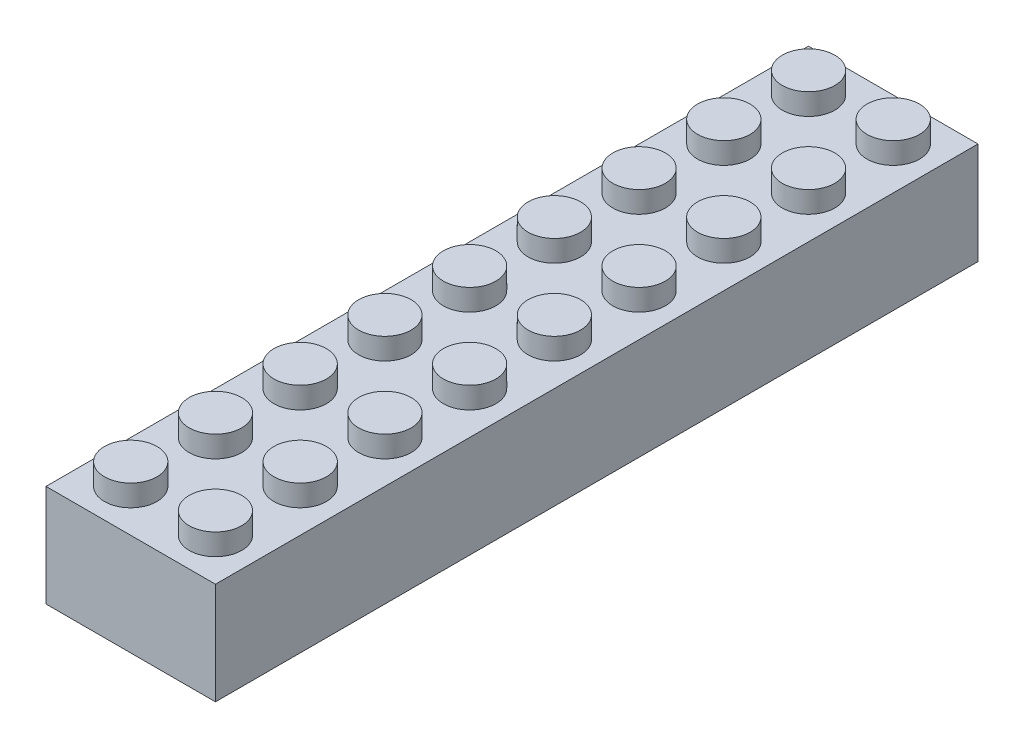
SolidWorks part; units mm, degrees
ref_plane "Front Plane" through (0, 0, 0) normal (0, 0, 1) x (1, 0, 0)
ref_plane "Top Plane" through (0, 0, 0) normal (0, 1, 0) x (1, 0, 0)
ref_plane "Right Plane" through (0, 0, 0) normal (1, 0, 0) x (0, 0, -1)
sketch "stencil" plane through (0, 0, 0) normal (0, 1, 0) x (1, 0, 0)
  line L2 (7.9, 71.1) -> (7.9, 0) construction
  line L29 (14.3, 1.5) -> (1.5, 1.5)
  line L30 (15.8, 71.1) -> (0, 71.1)
  line L32 (15.8, 71.1) -> (15.8, 0)
  line L34 (15.8, 0) -> (0, 0)
  line L36 (0, 71.1) -> (0, 0)
  line L37 (7.9, 0) -> (7.9, 71.1) construction
  line L38 (15.8, 35.55) -> (0, 35.55) construction
  line L39 (1.5, 69.6) -> (1.5, 1.5)
  line L40 (14.3, 69.6) -> (1.5, 69.6)
  line L41 (14.3, 69.6) -> (14.3, 1.5)
  circle A40 centre (3.95, 3.95) radius 2.45
  circle A41 centre (7.9, 7.9) radius 3.25
  circle A42 centre (3.95, 11.85) radius 2.45
  circle A43 centre (3.95, 19.75) radius 2.45
  circle A44 centre (3.95, 27.65) radius 2.45
  circle A45 centre (7.9, 15.8) radius 3.25
  circle A46 centre (7.9, 23.7) radius 3.25
  circle A47 centre (7.9, 31.6) radius 3.25
  circle A48 centre (3.95, 35.55) radius 2.45
  circle A49 centre (3.95, 43.45) radius 2.45
  circle A50 centre (3.95, 51.35) radius 2.45
  circle A51 centre (7.9, 39.5) radius 3.25
  circle A52 centre (7.9, 47.4) radius 3.25
  circle A53 centre (3.95, 59.25) radius 2.45
  circle A54 centre (3.95, 67.15) radius 2.45
  circle A55 centre (7.9, 55.3) radius 3.25
  circle A56 centre (7.9, 63.2) radius 3.25
  circle A57 centre (7.9, 7.9) radius 2.45
  circle A58 centre (7.9, 15.8) radius 2.45
  circle A59 centre (7.9, 23.7) radius 2.45
  circle A60 centre (7.9, 31.6) radius 2.45
  circle A61 centre (7.9, 39.5) radius 2.45
  circle A62 centre (7.9, 47.4) radius 2.45
  circle A63 centre (7.9, 55.3) radius 2.45
  circle A64 centre (7.9, 63.2) radius 2.45
  circle A65 centre (11.85, 11.85) radius 2.45
  circle A66 centre (11.85, 19.75) radius 2.45
  circle A67 centre (11.85, 27.65) radius 2.45
  circle A68 centre (11.85, 35.55) radius 2.45
  circle A69 centre (11.85, 43.45) radius 2.45
  circle A70 centre (11.85, 51.35) radius 2.45
  circle A71 centre (11.85, 59.25) radius 2.45
  circle A72 centre (11.85, 67.15) radius 2.45
  circle A73 centre (11.85, 3.95) radius 2.45
  point P1 (0, 0)
  point P6 (3.95, -15.8)
  point P9 (7.9, -15.8)
  point P10 (7.9, -11.85)
  point P13 (3.95, -7.9)
  point P15 (7.9, -7.9)
  point P17 (7.9, -3.95)
  point P18 (3.95, 0)
  point P21 (7.9, 0)
  point P25 (7.9, 3.95)
  point P27 (3.95, 7.9)
  point P28 (7.9, 7.9)
  point P29 (0, -11.85)
  point P30 (0, -7.9)
  point P31 (0, 3.95)
  point P34 (0, -3.95)
  point P35 (3.95, 0)
  point P36 (0, 15.8)
  point P37 (0, 23.7)
  point P38 (7.9, 23.7)
  point P39 (15.8, 23.7)
  point P40 (15.8, 15.8)
  point P41 (15.8, 7.9)
  point P43 (7.9, 0)
  point P48 (11.85, 0)
  point P49 (15.8, 0)
  point P50 (3.95, 3.95)
  point P51 (7.9, 3.95)
  point P52 (11.85, 3.95)
  point P53 (15.8, 3.95)
  point P54 (3.95, 7.9)
  point P55 (7.9, 7.9)
  point P56 (11.85, 7.9)
  point P57 (15.8, 7.9)
  point P58 (3.95, 11.85)
  point P59 (7.9, 11.85)
  point P60 (11.85, 11.85)
  point P61 (15.8, 11.85)
  point P63 (3.95, 15.8)
  point P64 (7.9, 15.8)
  point P65 (11.85, 15.8)
  point P66 (15.8, 15.8)
  point P67 (3.95, 19.75)
  point P68 (7.9, 19.75)
  point P69 (11.85, 19.75)
  point P70 (15.8, 19.75)
  point P71 (3.95, 23.7)
  point P72 (7.9, 23.7)
  point P73 (11.85, 23.7)
  point P75 (15.8, 23.7)
  point P77 (3.95, 27.65)
  point P79 (7.9, 27.65)
  point P81 (11.85, 27.65)
  point P83 (15.8, 27.65)
  point P85 (3.95, 31.6)
  point P87 (7.9, 31.6)
  point P88 (11.85, 31.6)
  point P89 (15.8, 31.6)
  point P90 (0, 3.95)
  point P91 (0, 7.9)
  point P92 (0, 11.85)
  point P93 (0, 15.8)
  point P94 (0, 19.75)
  point P95 (0, 23.7)
  point P96 (0, 27.65)
  point P97 (0, 31.6)
  point P113 (0, 35.55)
  point P114 (3.95, 35.55)
  point P115 (7.9, 35.55)
  point P116 (11.85, 35.55)
  point P117 (15.8, 35.55)
  point P118 (0, 39.5)
  point P119 (3.95, 39.5)
  point P120 (7.9, 39.5)
  point P121 (11.85, 39.5)
  point P122 (15.8, 39.5)
  point P124 (0, 43.45)
  point P125 (3.95, 43.45)
  point P126 (7.9, 43.45)
  point P127 (11.85, 43.45)
  point P128 (15.8, 43.45)
  point P129 (0, 47.4)
  point P130 (3.95, 47.4)
  point P131 (7.9, 47.4)
  point P132 (11.85, 47.4)
  point P133 (15.8, 47.4)
  point P135 (0, 51.35)
  point P136 (3.95, 51.35)
  point P137 (7.9, 51.35)
  point P138 (11.85, 51.35)
  point P139 (15.8, 51.35)
  point P140 (0, 55.3)
  point P141 (3.95, 55.3)
  point P142 (7.9, 55.3)
  point P143 (11.85, 55.3)
  point P144 (15.8, 55.3)
  point P145 (0, 59.25)
  point P146 (3.95, 59.25)
  point P147 (7.9, 59.25)
  point P148 (11.85, 59.25)
  point P149 (15.8, 59.25)
  point P150 (0, 63.2)
  point P151 (3.95, 63.2)
  point P152 (7.9, 63.2)
  point P153 (11.85, 63.2)
  point P154 (15.8, 63.2)
  point P165 (0, 67.15)
  point P166 (3.95, 67.15)
  point P167 (7.9, 67.15)
  point P168 (11.85, 67.15)
  point P169 (15.8, 67.15)
  point P170 (0, 71.1)
  point P171 (3.95, 71.1)
  point P172 (7.9, 71.1)
  point P173 (11.85, 71.1)
  point P174 (15.8, 71.1)
  point P182 (7.9, 35.55)
  dimension "D8" = 4.9
  dimension "D9" = 6.5
  dimension "D3" = 3.95
  dimension "D4" = 3.95
  dimension "D5" = 15.8
  dimension "D6" = 71.1
  dimension "D7" = 0.8
  dimension "D10" = 1.5
  dimension "D1" = 5
  dimension "D2" = 19
sketch "Sketch1" plane through (0, 0, 0) normal (0, 1, 0) x (1, 0, 0)
  line L1 (15.8, 71.1) -> (0, 71.1)
  line L2 (15.8, 71.1) -> (15.8, 0)
  line L3 (15.8, 0) -> (0, 0)
  line L4 (0, 71.1) -> (0, 0)
  line L5 (7.9, 0) -> (7.9, 71.1) construction
  line L6 (15.8, 35.55) -> (0, 35.55) construction
  point P0 (7.9, 35.55)
extrude "Boss-Extrude1" add sketch "Sketch1" along normal mid plane 9.5
sketch "Sketch2" plane through (0, 4.75, 0) normal (0, 1, 0) x (1, 0, 0)
  line L0 (0, 71.1) -> (0, 0) construction
  circle A0 centre (3.95, 3.95) radius 2.45
  circle A1 centre (11.85, 3.95) radius 2.45
  circle A2 centre (11.85, 11.85) radius 2.45
  circle A3 centre (3.95, 11.85) radius 2.45
  circle A4 centre (3.95, 19.75) radius 2.45
  circle A5 centre (3.95, 27.65) radius 2.45
  circle A6 centre (11.85, 27.65) radius 2.45
  circle A7 centre (11.85, 35.55) radius 2.45
  circle A8 centre (3.95, 35.55) radius 2.45
  circle A9 centre (3.95, 43.45) radius 2.45
  circle A10 centre (11.85, 43.45) radius 2.45
  circle A11 centre (3.95, 51.35) radius 2.45
  circle A12 centre (11.85, 51.35) radius 2.45
  circle A13 centre (3.95, 59.25) radius 2.45
  circle A14 centre (11.85, 59.25) radius 2.45
  circle A15 centre (3.95, 67.15) radius 2.45
  circle A16 centre (11.85, 67.15) radius 2.45
  circle A17 centre (3.95, 3.95) radius 2.45 construction
  circle A18 centre (11.85, 19.75) radius 2.45
  circle A19 centre (11.85, 19.75) radius 2.45 construction
extrude "Boss-Extrude2" add sketch "Sketch2" along normal blind 2
sketch "Sketch3" plane through (0, -4.75, 0) normal (0, -1, 0) x (1, 0, 0)
  line L1 (14.3, -1.5) -> (1.5, -1.5)
  line L2 (14.3, -1.5) -> (14.3, -69.6)
  line L3 (14.3, -69.6) -> (1.5, -69.6)
  line L4 (1.5, -1.5) -> (1.5, -69.6)
  line L5 (7.9, -69.6) -> (7.9, -1.5) construction
  line L6 (14.3, -35.55) -> (1.5, -35.55) construction
  point P0 (7.9, -35.55)
extrude "Cut-Extrude1" cut sketch "Sketch3" against normal blind 4
sketch "Sketch4" plane through (0, -0.75, 0) normal (0, -1, 0) x (1, 0, 0)
  circle A0 centre (7.9, -63.2) radius 3.25
  circle A1 centre (7.9, -55.3) radius 3.25
  circle A2 centre (7.9, -47.4) radius 3.25
  circle A3 centre (7.9, -39.5) radius 3.25
  circle A4 centre (7.9, -31.6) radius 3.25
  circle A5 centre (7.9, -23.7) radius 3.25
  circle A6 centre (7.9, -15.8) radius 3.25
  circle A7 centre (7.9, -7.9) radius 3.25
  circle A8 centre (7.9, -7.9) radius 2.45
  circle A10 centre (7.9, -15.8) radius 2.45
  circle A11 centre (7.9, -23.7) radius 2.45
  circle A12 centre (7.9, -31.6) radius 2.45
  circle A13 centre (7.9, -39.5) radius 2.45
  circle A14 centre (7.9, -47.4) radius 2.45
  circle A15 centre (7.9, -55.3) radius 2.45
  circle A16 centre (7.9, -63.2) radius 2.45
  circle A17 centre (7.9, -63.2) radius 2.45 construction
  circle A18 centre (7.9, -63.2) radius 3.25 construction
extrude "Boss-Extrude3" add sketch "Sketch4" along normal up to surface (4 mm away) up to face at (7.9, -4.75, -35.55)
equation "\"t\"= 0'tolerance"
equation "\"D5@stencil\"=15.80-\"t\""
equation "\"D10@stencil\"=1.5-\"t\""
equation "\"D6@stencil\"=71.10mm-\"t\""
equation "\"D1@Boss-Extrude1\"=9.50mm-\"t\""
equation "\"D9@stencil\"=6.5-\"t\""
